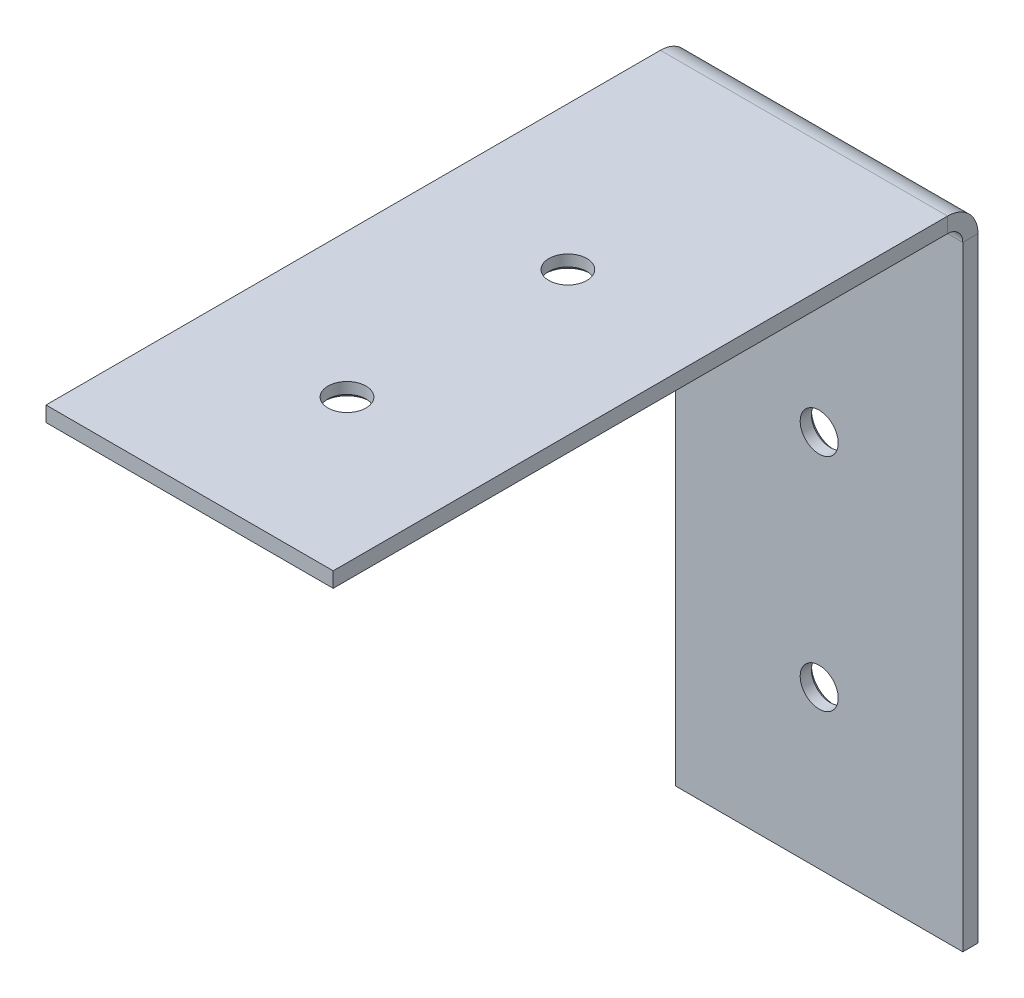
SolidWorks part; units mm, degrees
note: The reader was unsure of these and kept them because the rebuilt part matched: flange length of "Edge-Flange1".
ref_plane "Front Plane" through (0, 0, 0) normal (0, 0, 1) x (1, 0, 0)
ref_plane "Top Plane" through (0, 0, 0) normal (0, 1, 0) x (1, 0, 0)
ref_plane "Right Plane" through (0, 0, 0) normal (1, 0, 0) x (0, 0, -1)
sketch "Sketch1" plane through (0, 0, 0) normal (0, 0, 1) x (1, 0, 0)
  line L1 (-18.875, 41.38) -> (18.875, 41.38)
  line L2 (-18.875, 41.38) -> (-18.875, -41.38)
  line L3 (-18.875, -41.38) -> (18.875, -41.38)
  line L4 (18.875, 41.38) -> (18.875, -41.38)
  line L5 (-18.875, 41.38) -> (18.875, -41.38) construction
  line L6 (-18.875, -41.38) -> (18.875, 41.38) construction
  point P0 (0, 0)
  dimension "D1" = 37.75
  dimension "D2" = 82.76
base flange "Base-Flange1" sketch "Sketch1" thickness 2 reverse thickness direction no parameters "D1"=2
edge flange "Edge-Flange1" sketch "Sketch8" flange angle 90 flange length 84.76 flange position material outside bend radius 2 thickness 2 relief rectangular parameters "D6"=10
sketch "Sketch8" plane through (0, 41.38, 0) normal (0, -1, 0) x (1, 0, 0)
  line L2 (-18.875, 0) -> (-18.875, 82.76)
  line L3 (-18.875, 82.76) -> (18.875, 82.76)
  line L4 (18.875, 82.76) -> (18.875, 0)
  line L5 (18.875, 0) -> (-18.875, 0) construction
  line L6 (18.875, 0) -> (-18.875, 0)
  dimension "D1" = 82.76
bend "EdgeBend1" bend radius 2 bend angle 90 parameters "D5"=1
sketch "Sketch11" plane through (0, 0, -2) normal (0, 0, -1) x (-1, 0, 0)
  line L0 (0, 39.38) -> (0, -41.38) construction
  line L1 (18.875, 39.38) -> (-18.875, 39.38) construction
  line L2 (18.875, -41.38) -> (-18.875, -41.38) construction
  line L3 (18.875, -20.69) -> (-18.875, -20.69) construction
  line L4 (18.875, 39.38) -> (18.875, -41.38) construction
  line L5 (-18.875, -41.38) -> (-18.875, 39.38) construction
  line L6 (18.875, 8.345) -> (-18.875, 8.345) construction
  dimension "D1" = 20.69
  dimension "D2" = 31.035
sketch "Sketch14" plane through (0, 0, -2) normal (0, 0, -1) x (-1, 0, 0)
  line L0 (18.875, 8.345) -> (-18.875, 8.345) construction
  line L1 (18.875, -20.69) -> (-18.875, -20.69) construction
  point P0 (0, 8.345)
  point P4 (0, -20.69)
hole_wizard "M6x1.0 Tapped Hole2" positions "Sketch14" profile "Sketch13" tap size "M6x1.0" standard "ANSI Metric"
sketch "Sketch13" plane through (0, 8.345, -2) normal (1, 0, 0) x (0, 1, 0)
  line L0 (0, 0) -> (0, 16.5022)
  line L1 (0, 16.5022) -> (2.5, 15)
  line L2 (2.5, 15) -> (2.5, 0.525)
  line L3 (2.5, 0.525) -> (3.025, 0)
  line L5 (3.025, 0) -> (0, 0)
  line L6 (-2.5, 0.525) -> (-3.025, 0) construction
  line L10 (0, 16.5022) -> (-2.5, 15) construction
  line L11 (0, -6.35) -> (0, 107.95) construction
  dimension "Tap Drill Dia." = 5
  dimension "Tap Drill Depth" = 15
  dimension "Near C'Sink Dia." = 6.05
  dimension "Near C'Sink Angle" = 90
  dimension "Drill Angle" = 118
cosmetic thread "Hole Thread10"
cosmetic thread "Hole Thread11"
sketch "Sketch23" plane through (0, 41.38, 0) normal (0, -1, 0) x (-1, 0, 0)
  line L0 (-18.875, -2) -> (18.875, -2) construction
  line L1 (-18.875, -82.76) -> (18.875, -82.76) construction
  line L2 (18.875, -82.76) -> (18.875, -2) construction
  point P0 (0, -33.035)
  point P2 (0, -62.07)
  dimension "D1" = 31.035
  dimension "D2" = 20.69
  dimension "D3" = 18.875
  dimension "D4" = 18.875
hole_wizard "M6x1.0 Tapped Hole3" positions "Sketch23" profile "Sketch22" tap size "M6x1.0" standard "ANSI Metric"
sketch "Sketch22" plane through (0, 41.38, 33.035) normal (1, 0, 0) x (0, 0, -1)
  line L0 (0, 0) -> (0, 16.5022)
  line L1 (0, 16.5022) -> (2.5, 15)
  line L2 (2.5, 15) -> (2.5, 0.525)
  line L3 (2.5, 0.525) -> (3.025, 0)
  line L5 (3.025, 0) -> (0, 0)
  line L6 (-2.5, 0.525) -> (-3.025, 0) construction
  line L10 (0, 16.5022) -> (-2.5, 15) construction
  line L11 (0, -6.35) -> (0, 107.95) construction
  dimension "Tap Drill Dia." = 5
  dimension "Tap Drill Depth" = 15
  dimension "Near C'Sink Dia." = 6.05
  dimension "Near C'Sink Angle" = 90
  dimension "Drill Angle" = 118
cosmetic thread "Hole Thread15"
cosmetic thread "Hole Thread16"
sketch "Bend-Lines1" [suppressed] plane through (0, 0, 0) normal (0, 1, 0) x (1, 0, 0)
sketch "Bounding-Box1" [suppressed] plane through (0, 0, 0) normal (0, 1, 0) x (1, 0, 0)
sheet metal parameters "Sheet-Metal1" thickness 2 parameters "D1"=2
flat pattern "Flat-Pattern1" [suppressed]
sketch "Bend-Lines2" plane through (0, 0, 0) normal (0, 1, 0) x (1, 0, 0)
sketch3d "Bounding-Box2" [suppressed]
  line L0 (-18.875, 20.69, 0) -> (-18.875, -20.69, 0) construction
  line L1 (18.875, 20.69, 0) -> (18.875, -20.69, 0) construction
  line L2 (-18.875, 20.69, 0) -> (18.875, 20.69, 0) construction
  line L3 (-18.875, -20.69, 0) -> (18.875, -20.69, 0) construction
sheet metal parameters "Sheet-Metal2" thickness 2 parameters "D1"=2
flat pattern "Flat-Pattern1"
sketch "Bend-Lines2" plane through (0, 0, 0) normal (0, 0, 1) x (1, 0, 0)
  line L0 (18.875, 21.0462) -> (-18.875, 21.0462) construction
  line L1 (18.875, 21.0462) -> (-18.875, 21.0462) construction
sketch3d "Bounding-Box2" [suppressed]
  line L0 (18.875, 60.7824, 0) -> (18.875, -20.69, 0) construction
  line L1 (-18.875, 60.7824, 0) -> (-18.875, -20.69, 0) construction
  line L2 (18.875, 60.7824, 0) -> (-18.875, 60.7824, 0) construction
  line L3 (18.875, -20.69, 0) -> (-18.875, -20.69, 0) construction
bend of the flat pattern "Flatten-<EdgeBend1>1"
sheet metal parameters "Sheet-Metal5" thickness 2 parameters "D1"=2
flat pattern "Flat-Pattern1"
sketch "Bend-Lines2" plane through (0, 0, 0) normal (0, 0, 1) x (1, 0, 0)
  line L0 (18.875, 41.7362) -> (-18.875, 41.7362) construction
  line L1 (18.875, 41.7362) -> (-18.875, 41.7362) construction
sketch3d "Bounding-Box2" [suppressed]
  line L0 (18.875, 124.8524, 0) -> (18.875, -41.38, 0) construction
  line L1 (-18.875, 124.8524, 0) -> (-18.875, -41.38, 0) construction
  line L2 (18.875, 124.8524, 0) -> (-18.875, 124.8524, 0) construction
  line L3 (18.875, -41.38, 0) -> (-18.875, -41.38, 0) construction
bend of the flat pattern "Flatten-<EdgeBend1>1"
sheet metal parameters "Sheet-Metal7" thickness 2 parameters "D1"=2
flat pattern "Flat-Pattern1"
sketch "Bend-Lines2" plane through (0, 0, 0) normal (0, 0, 1) x (1, 0, 0)
  line L0 (18.875, 41.7362) -> (-18.875, 41.7362) construction
  line L1 (18.875, 41.7362) -> (-18.875, 41.7362) construction
sketch3d "Bounding-Box2" [suppressed]
  line L0 (18.875, 124.8524, 0) -> (18.875, -41.38, 0) construction
  line L1 (-18.875, 124.8524, 0) -> (-18.875, -41.38, 0) construction
  line L2 (18.875, 124.8524, 0) -> (-18.875, 124.8524, 0) construction
  line L3 (18.875, -41.38, 0) -> (-18.875, -41.38, 0) construction
bend of the flat pattern "Flatten-<EdgeBend1>1"
